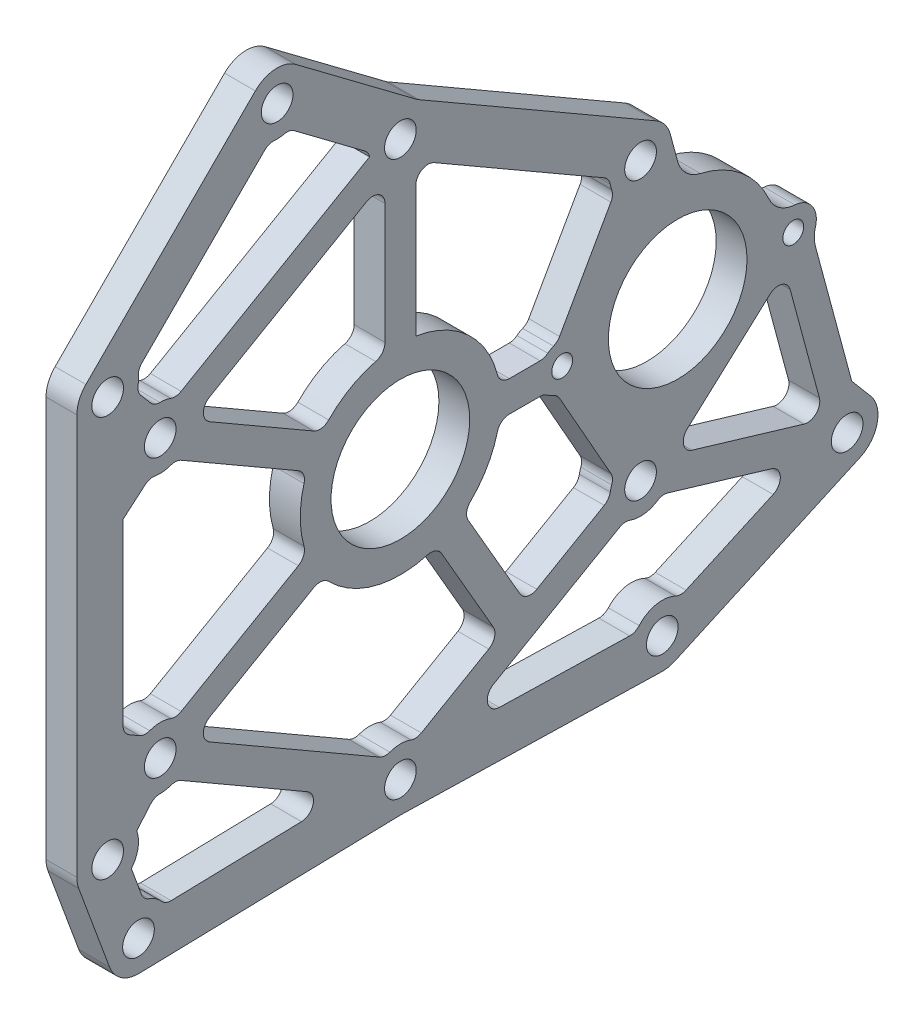
SolidWorks part; units mm, degrees
material "6061-T6 (SS)"
ref_plane "Front Plane" through (0, 0, 0) normal (0, 0, 1) x (1, 0, 0)
ref_plane "Top Plane" through (0, 0, 0) normal (0, 1, 0) x (1, 0, 0)
ref_plane "Right Plane" through (0, 0, 0) normal (1, 0, 0) x (0, 0, -1)
sketch "Sketch1" plane through (0, 0, 0) normal (1, 0, 0) x (0, 0, -1)
  line L0 (-60.325, 41.275) -> (-25.4, 76.2) construction
  line L1 (-25.4, 76.2) -> (0, 57.15) construction
  line L2 (0, 57.15) -> (49.4934, 28.575) construction
  line L3 (49.4934, 28.575) -> (57.15, 0) construction
  line L4 (57.15, 0) -> (92.075, -41.275) construction
  line L5 (92.075, -41.275) -> (53.975, -58.4932) construction
  line L6 (53.975, -58.4932) -> (0, -57.15) construction
  line L7 (0, -57.15) -> (-53.975, -58.4932) construction
  line L8 (-53.975, -58.4932) -> (-60.325, -41.275) construction
  line L9 (-60.325, -41.275) -> (-60.325, 41.275) construction
  line L10 (-66.675, -41.275) -> (-66.675, 41.275)
  line L11 (-64.8151, 45.7651) -> (-29.8901, 80.6901)
  line L12 (-21.59, 81.28) -> (3.2002, 62.6874)
  line L13 (3.8352, 62.2681) -> (52.6684, 34.0743)
  line L14 (55.627, 30.2185) -> (62.9157, 3.0166)
  line L15 (62.9157, 3.0166) -> (96.9225, -37.1733)
  line L16 (94.6901, -47.0615) -> (56.5901, -64.2797)
  line L17 (53.817, -64.8412) -> (0.158, -63.5059)
  line L18 (-0.158, -63.5059) -> (-53.817, -64.8412)
  line L19 (-59.9328, -60.6904) -> (-66.2828, -43.4722)
  line L20 (-66.675, -42.4086) -> (-66.675, 43.9053) construction
  line L21 (-58.3602, -64.9543) -> (-66.675, -42.4086) construction
  line L22 (0, -63.502) -> (-58.3602, -64.9543) construction
  line L23 (55.2677, -64.8773) -> (0, -63.502) construction
  line L24 (102.3575, -43.5965) -> (55.2677, -64.8773) construction
  line L25 (62.9157, 3.0166) -> (102.3575, -43.5965) construction
  line L26 (3.5051, 62.4587) -> (54.9462, 32.7591) construction
  line L27 (54.9462, 32.7591) -> (62.9157, 3.0166) construction
  line L28 (-25.9959, 84.5844) -> (3.5051, 62.4587) construction
  line L29 (-66.675, 43.9053) -> (-25.9959, 84.5844) construction
  line L30 (80.9625, 0) -> (92.075, -41.275) construction
  line L31 (84.0283, 0.8254) -> (95.1408, -40.4496)
  circle A0 centre (53.975, -58.4932) radius 3.2639 construction
  circle A1 centre (-53.975, -58.4932) radius 3.2639 construction
  circle A2 centre (-25.4, 76.2) radius 3.2639 construction
  circle A3 centre (-49.4934, -28.575) radius 3.2639 construction
  circle A4 centre (49.4934, -28.575) radius 3.2639 construction
  circle A5 centre (0, -57.15) radius 3.2639 construction
  circle A6 centre (0, 57.15) radius 3.2639 construction
  circle A7 centre (49.4934, 28.575) radius 3.2639 construction
  circle A8 centre (-49.4934, 28.575) radius 3.2639 construction
  circle A9 centre (0, 0) radius 14.2875 construction
  circle A10 centre (57.15, 0) radius 14.2875 construction
  circle A11 centre (92.075, -41.275) radius 3.2639 construction
  circle A12 centre (-60.325, -41.275) radius 3.2639 construction
  circle A13 centre (-60.325, 41.275) radius 3.2639 construction
  circle A14 centre (53.975, -58.4932) radius 3.2639
  circle A15 centre (-53.975, -58.4932) radius 3.2639
  circle A16 centre (-25.4, 76.2) radius 3.2639
  circle A17 centre (-49.4934, -28.575) radius 3.2639
  circle A18 centre (49.4934, -28.575) radius 3.2639
  circle A19 centre (0, -57.15) radius 3.2639
  circle A20 centre (0, 57.15) radius 3.2639
  circle A21 centre (49.4934, 28.575) radius 3.2639
  circle A22 centre (-49.4934, 28.575) radius 3.2639
  circle A23 centre (0, 0) radius 14.2875
  circle A24 centre (57.15, 0) radius 14.2875
  circle A25 centre (92.075, -41.275) radius 3.2639
  circle A26 centre (-60.325, -41.275) radius 3.2639
  circle A27 centre (-60.325, 41.275) radius 3.2639
  circle A28 centre (57.15, 0) radius 20.6375
  arc A29 (-66.675, -41.275) -> (-66.2828, -43.4722) centre (-60.325, -41.275) ccw
  arc A30 (-53.817, -64.8412) -> (-59.9328, -60.6904) centre (-53.975, -58.4932) cw
  arc A31 (0.158, -63.5059) -> (-0.158, -63.5059) centre (0, -69.8539) ccw
  arc A32 (56.5901, -64.2797) -> (53.817, -64.8412) centre (53.975, -58.4932) cw
  arc A33 (96.9225, -37.1733) -> (94.6901, -47.0615) centre (92.075, -41.275) cw
  arc A34 (52.6684, 34.0743) -> (55.627, 30.2185) centre (49.4934, 28.575) cw
  arc A35 (3.2002, 62.6874) -> (3.8352, 62.2681) centre (7.0102, 67.7674) ccw
  arc A36 (-29.8901, 80.6901) -> (-21.59, 81.28) centre (-25.4, 76.2) cw
  arc A37 (-66.675, 41.275) -> (-64.8151, 45.7651) centre (-60.325, 41.275) cw
  circle A38 centre (80.9625, 0) radius 2.1463 construction
  circle A39 centre (33.3375, 0) radius 2.1463 construction
  circle A40 centre (80.9625, 0) radius 2.1463
  circle A41 centre (33.3375, 0) radius 2.1463
  circle A42 centre (80.9625, 0) radius 4.7625
  dimension "D3" = 6.35
  dimension "D4" = 9.525
  dimension "D1" = 6.35
  dimension "D2" = 6.35
  dimension "D5" = 3.175
extrude "Boss-Extrude1" add sketch "Sketch1" along normal blind 6.35 contours A28 L14 L13 L12 L11 L10 L19 L18 L17 L16 L15 A27 A26 A25 A23 A22 A21 A20 A19 A18 A17 A16 A15 A14 | L15 A28 L14 A24 | L14 A28 L15 A24 | A28 A42 | A28 A42 A40 | A42 A28 L15 L31 region at (0, 0, 64.4618) region at (0, 7.192, -70.216) region at (0, 17.163, -58.5432) region at (0, 4.3028, -82.6905) region at (0, 0, -77.0913) region at (0, -14.6669, -83.743)
fillet "Fillet1" radius 6.35 3 edges at (3.175, 20.6107, -58.2014) (3.175, 3.294, -77.5229) (3.175, -2.6023, -84.9512)
sketch "Sketch2" plane through (6.35, 0, 0) normal (1, 0, 0) x (0, 0, -1)
  line L0 (-60.325, 41.275) -> (-49.4934, 28.575) construction
  line L2 (-49.4934, -28.575) -> (-60.325, -41.275) construction
  line L3 (-60.325, -41.275) -> (-53.975, -58.4932) construction
  line L4 (-53.975, -58.4932) -> (0, -57.15) construction
  line L5 (0, -57.15) -> (53.975, -58.4932) construction
  line L6 (53.975, -58.4932) -> (92.075, -41.275) construction
  line L7 (92.075, -41.275) -> (49.4934, -28.575) construction
  line L8 (49.4934, -28.575) -> (33.3375, 0) construction
  line L9 (33.3375, 0) -> (0, 0) construction
  line L10 (-49.4934, -28.575) -> (0, 0) construction
  line L11 (0, 0) -> (0, -57.15) construction
  line L12 (-49.4934, -28.575) -> (0, -57.15) construction
  line L13 (0, -57.15) -> (49.4934, -28.575) construction
  line L14 (-60.325, 41.275) -> (-25.4, 76.2) construction
  line L15 (-25.4, 76.2) -> (0, 57.15) construction
  line L16 (0, 57.15) -> (49.4934, 28.575) construction
  line L17 (49.4934, 28.575) -> (33.3375, 0) construction
  line L18 (49.4934, -28.575) -> (80.9625, 0) construction
  line L19 (80.9625, 0) -> (92.075, -41.275) construction
  line L20 (-49.4934, 28.575) -> (0, 0) construction
  line L21 (0, 0) -> (0, 57.15) construction
  line L22 (0, 57.15) -> (-49.4934, 28.575) construction
  line L23 (-60.325, 41.275) -> (-60.325, -41.275) construction
  line L34 (-58.0799, 39.0299) -> (-25.1021, 72.0078)
  line L35 (-25.1021, 72.0078) -> (-1.905, 54.61)
  line L36 (-62.7407, 39.2147) -> (-51.9091, 26.5147)
  line L37 (-1.5875, 59.8996) -> (-51.0809, 31.3246)
  line L38 (-51.0809, 25.8254) -> (-1.5875, -2.7496)
  line L39 (3.175, 0) -> (3.175, 57.15)
  line L40 (-1.5875, 54.4004) -> (45.1809, 27.3986)
  line L41 (45.1809, 27.3986) -> (30.5737, 1.5626)
  line L42 (33.3375, 3.175) -> (0, 3.175)
  line L43 (-47.9059, -31.3246) -> (1.5875, -2.7496)
  line L44 (-63.5, 41.275) -> (-63.5, -41.275)
  line L45 (-51.9091, -26.5147) -> (-62.7407, -39.2147)
  line L46 (-63.3039, -42.3736) -> (-56.1676, -61.7237)
  line L47 (-56.1676, -61.7237) -> (0.079, -60.324)
  line L48 (-51.0809, -31.3246) -> (-1.5875, -59.8996)
  line L49 (1.5875, -59.8996) -> (51.0809, -31.3246)
  line L50 (-0.079, -60.324) -> (54.6213, -61.6853)
  line L51 (54.6213, -61.6853) -> (93.3825, -44.1683)
  line L52 (92.9824, -38.2324) -> (50.4008, -25.5324)
  line L53 (51.6277, -30.9255) -> (79.2482, -5.8453)
  line L54 (79.2482, -5.8453) -> (89.0092, -42.1004)
  line L55 (52.2572, -27.0124) -> (36.1013, 1.5626)
  line L56 (-62.5701, 43.5201) -> (-25.6979, 80.3922)
  line L57 (-25.6979, 80.3922) -> (1.905, 59.69)
  line L58 (-57.9093, 43.3353) -> (-47.0776, 30.6353)
  line L59 (1.5875, 54.4004) -> (-47.9059, 25.8254)
  line L60 (-47.9059, 31.3246) -> (1.5875, 2.7496)
  line L61 (-3.175, 0) -> (-3.175, 57.15)
  line L62 (1.5875, 59.8996) -> (53.8058, 29.7514)
  line L63 (53.8058, 29.7514) -> (36.1013, -1.5626)
  line L64 (33.3375, -3.175) -> (0, -3.175)
  line L65 (-51.0809, -25.8254) -> (-1.5875, 2.7496)
  line L66 (-57.15, 41.275) -> (-57.15, -41.275)
  line L67 (-47.0776, -30.6353) -> (-57.9093, -43.3353)
  line L68 (-57.3461, -40.1764) -> (-51.7824, -55.2626)
  line L69 (-51.7824, -55.2626) -> (-0.079, -53.976)
  line L70 (-47.9059, -25.8254) -> (1.5875, -54.4004)
  line L71 (-1.5875, -54.4004) -> (47.9059, -25.8254)
  line L72 (0.079, -53.976) -> (53.3287, -55.3011)
  line L73 (53.3287, -55.3011) -> (90.7675, -38.3817)
  line L74 (91.1676, -44.3176) -> (48.5859, -31.6176)
  line L75 (47.359, -26.2245) -> (82.6768, 5.8453)
  line L76 (82.6768, 5.8453) -> (95.1408, -40.4496)
  line L77 (46.7295, -30.1376) -> (30.5737, -1.5626)
  line L78 (-49.4934, 28.575) -> (-60.325, 19.3368) construction
  line L79 (-49.4934, -28.575) -> (-60.325, -22.3213) construction
  line L80 (-51.5537, 30.9907) -> (-62.3853, 21.7526)
  line L81 (-47.9059, -25.8254) -> (-58.7375, -19.5717)
  line L82 (-47.433, 26.1593) -> (-58.2647, 16.9211)
  line L83 (-51.0809, -31.3246) -> (-61.9125, -25.071)
  line L84 (0, 0) -> (24.7467, -42.8625) construction
  line L85 (-2.7496, -1.5875) -> (21.997, -44.45)
  line L86 (2.7496, 1.5875) -> (27.4963, -41.275)
  circle A9 centre (-60.325, 41.275) radius 6.35
  circle A10 centre (-25.4, 76.2) radius 6.35
  circle A11 centre (0, 57.15) radius 6.35
  circle A12 centre (-49.4934, 28.575) radius 6.35
  circle A13 centre (-49.4934, -28.575) radius 6.35
  circle A14 centre (-60.325, -41.275) radius 6.35
  circle A15 centre (-53.975, -58.4932) radius 6.35
  circle A16 centre (0, -57.15) radius 6.35
  circle A17 centre (49.4934, -28.575) radius 6.35
  circle A18 centre (49.4934, 28.575) radius 6.35
  circle A19 centre (92.075, -41.275) radius 6.35
  circle A20 centre (80.9625, 0) radius 4.7625
  circle A21 centre (53.975, -58.4932) radius 6.35
  circle A22 centre (33.3375, 0) radius 4.7625
  arc A23 (85.542, -1.3075) -> (81.3027, 4.7503) centre (80.9625, 0) ccw construction
  circle A38 centre (0, 0) radius 20.6375
  circle A39 centre (57.15, 0) radius 17.4625
  dimension "D1" = 12.7
  dimension "D2" = 3.175
  dimension "D4" = 41.275
  dimension "D5" = 34.925
  dimension "D10" = 9.525
  dimension "D3" = 3.175
  dimension "D6" = 3.175
  dimension "D7" = 3.175
  dimension "D8" = 3.175
  dimension "D9" = 3.175
extrude "Cut-Extrude1" cut sketch "Sketch2" against normal through all contours A38 L61 L59 L60 | A12 L37 A11 L35 A10 L34 A9 L58 | A38 L42 A22 L41 A18 L40 L39 | A38 L43 L70 A16 L71 A17 L77 A22 L64 | A15 L69 L48 A13 L67 A14 L68 | A20 L53 L52 L54 | A21 L73 L74 A17 L49 L72 | A38 L38 A12 L36 L66 L45 A13 L65 | A38 L43 L70 A16 L71 L85 region at (6.35, 52.4533, 31.4692) region at (6.35, -0.1562, 41.322) region at (6.35, 30.6181, 17.6774) region at (6.35, -46.9188, 38.9282) region at (6.35, 25.8285, -21.2307) region at (6.35, -32.7094, 8.558) region at (6.35, -19.9562, -28.3431) region at (6.35, -45.4109, -48.3641) region at (6.35, -23.1976, -74.1911)
fillet "Fillet2" radius 2.54 51 edges at (3.175, -36.6062, -87.53) (3.175, -5.8453, -79.2482) (3.175, -27.1413, -55.7952) (3.175, -55.1824, -48.5564) (3.175, -53.3352, -57.6788) (3.175, -41.8857, -83.0139) (3.175, -33.1893, -53.8558) (3.175, -34.0743, -46.3184) (3.175, -54.2567, -11.3613) (3.175, 51.6507, -3.175) (3.175, 28.575, -43.1434) (3.175, 25.3505, -44.023) (3.175, 4.6527, -32.3207) (3.175, 3.175, -29.7877) (3.175, 3.175, -20.3918) (3.175, -3.175, -20.3918) (3.175, -3.175, -29.7877) (3.175, -4.6527, -32.3207) (3.175, -25.3505, -44.023) (3.175, -28.575, -43.1434) (3.175, -38.5254, -25.9088) (3.175, -16.0723, -12.9455) (3.175, 34.8195, 50.6462) (3.175, 34.0743, 46.3184) (3.175, 39.1512, 54.3407) (3.175, 42.9185, 54.1914) (3.175, 70.3604, 22.9056) (3.175, 70.0664, 27.0435) (3.175, 57.9096, 6.3044) (3.175, 51.6507, 3.175) (3.175, 20.3918, 3.175) (3.175, 12.9455, 16.0723) (3.175, 28.575, 43.1434) (3.175, -20.4883, 57.15) (3.175, -23.0757, 46.3184) (3.175, -23.0757, 52.6684) (3.175, 23.0757, 46.3184) (3.175, 22.5907, 51.6172) (3.175, 7.4463, 19.2473) (3.175, -7.4463, 19.2473) (3.175, -51.6507, 3.175) (3.175, -51.6507, -3.175) (3.175, -19.2473, -7.4463) (3.175, -41.7004, -20.4095) (3.175, -12.9455, 16.0723) (3.175, -28.575, 43.1434) (3.175, -52.235, 52.899) (3.175, -55.1824, 48.5564) (3.175, -54.2567, 11.3613) (3.175, -34.0743, 46.3184) (3.175, -34.8195, 50.6462)
